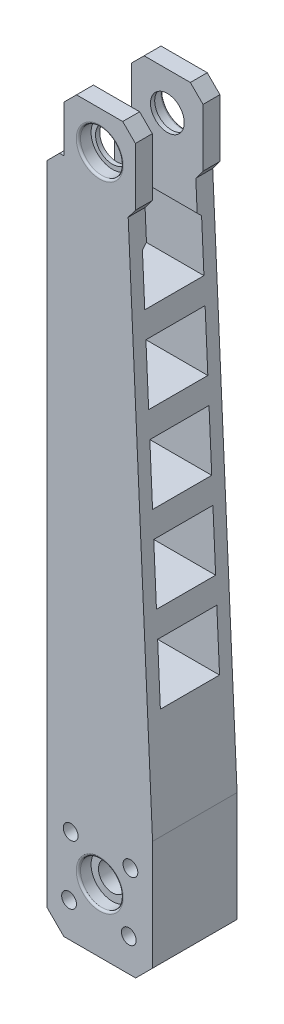
SolidWorks part; units mm, degrees
ref_plane "前视基准面" through (0, 0, 0) normal (0, 0, 1) x (1, 0, 0)
ref_plane "上视基准面" through (0, 0, 0) normal (0, 1, 0) x (1, 0, 0)
ref_plane "右视基准面" through (0, 0, 0) normal (1, 0, 0) x (0, 0, -1)
other "Configuration Table"
sketch "草图1" plane through (0, 0, 0) normal (0, 0, 1) x (1, 0, 0)
  line L0 (0, 82.6686) -> (0, -24.2482) construction
  line L5 (12.5, -50) -> (6.5, 80)
  line L6 (-12.5, -80) -> (12.5, -80)
  line L7 (-12.5, -80) -> (-12.5, 80)
  line L8 (-12.5, 80) -> (6.5, 80)
  line L9 (12.5, -80) -> (12.5, -50)
  line L10 (-12.5, -80) -> (7.8682, 50.3563) construction
  line L11 (-12.5, 80) -> (12.5, -80) construction
  circle A5 centre (0, -65) radius 10 construction
  circle A11 centre (-6.8811, -57.7439) radius 1.75
  circle A12 centre (7.2561, -58.1189) radius 1.75
  circle A13 centre (6.8811, -72.2561) radius 1.75
  circle A14 centre (-7.2561, -71.8811) radius 1.75
  point P1 (0, 0)
  point P21 (0, -70)
  point P24 (0, -65)
  dimension "D2" = 15
  dimension "D3" = 20
  dimension "D4" = 3.5
  dimension "D1" = 160
  dimension "D6" = 25
  dimension "D7" = 19
  dimension "D8" = 30
  dimension "D5" = 4
extrude "凸台-拉伸1" add sketch "草图1" along normal blind 20
chamfer "倒角1" distance 4 angle 45 2 edges at (-12.5, -80, 10) (12.5, -80, 10)
sketch "草图2" plane through (0, 0, 20) normal (0, 0, 1) x (1, 0, 0)
  line L0 (7.2561, -58.1189) -> (-7.2561, -71.8811) construction
  circle A0 centre (0, -65) radius 5.05
  dimension "D1" = 10.1
extrude "切除-拉伸1" cut sketch "草图2" against normal blind 3
sketch "草图3" plane through (0, 0, 0) normal (0, 0, -1) x (-1, 0, 0)
  line L0 (-7.2561, -58.1189) -> (7.2561, -71.8811) construction
  circle A0 centre (0, -65) radius 3.3
  dimension "D1" = 6.6
extrude "切除-拉伸2" cut sketch "草图3" against normal blind 32
sketch "草图4" plane through (0, 0, 0) normal (0, 0, -1) x (-1, 0, 0)
  circle A0 centre (0, -65) radius 5.05
  dimension "D1" = 10.1
extrude "切除-拉伸3" cut sketch "草图4" against normal blind 3
chamfer "倒角2" distance 3 angle 45 2 edges at (6.5, 80, 10) (-12.5, 80, 10)
sketch "草图6" plane through (-12.5, 0, 0) normal (-1, 0, 0) x (0, 0, 1)
  line L0 (10, 80.2056) -> (10, 66.0246) construction
  line L1 (3, 69) -> (4, 69)
  line L2 (3, 55) -> (17, 55)
  line L7 (3, 55) -> (3, 69)
  line L9 (17, 55) -> (17, 69)
  line L10 (3, 55) -> (17, 69) construction
  line L11 (3, 69) -> (17, 55) construction
  line L12 (3, 35) -> (3, 49)
  line L13 (3, 35) -> (17, 35)
  line L14 (17, 35) -> (17, 49)
  line L15 (3, 49) -> (17, 49)
  line L16 (3, 15) -> (3, 29)
  line L17 (3, 15) -> (17, 15)
  line L18 (17, 15) -> (17, 29)
  line L19 (3, 29) -> (17, 29)
  line L20 (3, -5) -> (3, 9)
  line L21 (3, -5) -> (17, -5)
  line L22 (17, -5) -> (17, 9)
  line L23 (3, 9) -> (17, 9)
  line L24 (3, -25) -> (3, -11)
  line L25 (3, -25) -> (17, -25)
  line L26 (17, -25) -> (17, -11)
  line L27 (3, -11) -> (17, -11)
  line L28 (4, 69) -> (4, 86.6068)
  line L29 (17, 69) -> (16, 69)
  line L30 (16, 69) -> (16, 86.6068)
  line L31 (4, 86.6068) -> (16, 86.6068)
  line L32 (20, 77) -> (20, -76) construction
  point P1 (10, 62)
  dimension "D1" = 14
  dimension "D2" = 4
  dimension "D4" = 5
extrude "切除-拉伸4" cut sketch "草图6" against normal blind 58
sketch "草图7" plane through (0, 0, 0) normal (0, 0, -1) x (-1, 0, 0)
  line L6 (8.5, 93.9753) -> (-4.4753, 93.9753)
  line L8 (-3.3515, 80) -> (-6.6383, 77.0032) construction
  line L9 (-4.4753, 78.9753) -> (-3.3515, 80)
  line L10 (-3.3515, 80) -> (8.5, 80)
  line L13 (-6.6383, 93.9753) -> (-4.4753, 93.9753)
  line L14 (-6.6383, 77.0032) -> (-4.4753, 78.9753)
  line L15 (-6.6383, 77.0032) -> (-6.7308, 75)
  line L16 (-12.5, -50) -> (-6.6383, 77.0032) construction
  line L17 (-6.7308, 75) -> (-8.4383, 77.2876)
  line L18 (-8.4383, 77.2876) -> (-8.4383, 93.9753)
  line L19 (-8.4383, 93.9753) -> (-6.6383, 93.9753)
  line L20 (8.5, 93.9753) -> (8.5, 80)
  dimension "D1" = 1.8
  dimension "D2" = 15
  dimension "D3" = 5
  dimension "D4" = 1
extrude "凸台-拉伸2" add sketch "草图7" against normal blind 4
ref_plane "基准面1" through (0, 0, 10) normal (0, 0, 1) x (1, 0, 0)
mirror "镜向1" about plane through (0, 0, 10) normal (0, 0, 1) of "凸台-拉伸2"
sketch "草图8" plane through (0, 0, 0) normal (0, 0, -1) x (-1, 0, 0)
  line L0 (0, -65) -> (0, -55.0194) construction
  line L1 (8.5, -80) -> (-8.5, -80) construction
  circle A0 centre (0, 85) radius 5.05
  dimension "D1" = 10.1
  dimension "D2" = 165
extrude "切除-拉伸5" cut sketch "草图8" against normal blind 3
sketch "草图9" plane through (0, 0, 3) normal (0, 0, -1) x (-1, 0, 0)
  circle A0 centre (0, 85) radius 4
  dimension "D1" = 8
extrude "切除-拉伸6" cut sketch "草图9" against normal blind 3
mirror "镜向2" about plane through (0, 0, 10) normal (0, 0, 1) of "切除-拉伸6", "切除-拉伸5"
chamfer "倒角3" distance 3 angle 45 2 edges at (-8.5, 93.9753, 2) (8.4383, 93.9753, 2)
chamfer "倒角4" distance 3 angle 45 2 edges at (-8.5, 93.9753, 18) (8.4383, 93.9753, 18)
chamfer "倒角5" distance 2 angle 45 2 edges at (-2.7462, 69, 3) (-2.7462, 69, 17)
fillet "圆角1" radius 0.5 1 edges at (-5.05, -65, 0)
fillet "圆角2" radius 0.5 1 edges at (5.05, -65, 20)
fillet "圆角3" radius 0.5 2 edges at (-5.05, 85, 0) (-5.05, 85, 20)
equation "\"3》9\"=10"
equation "\"3。9\"=10"
